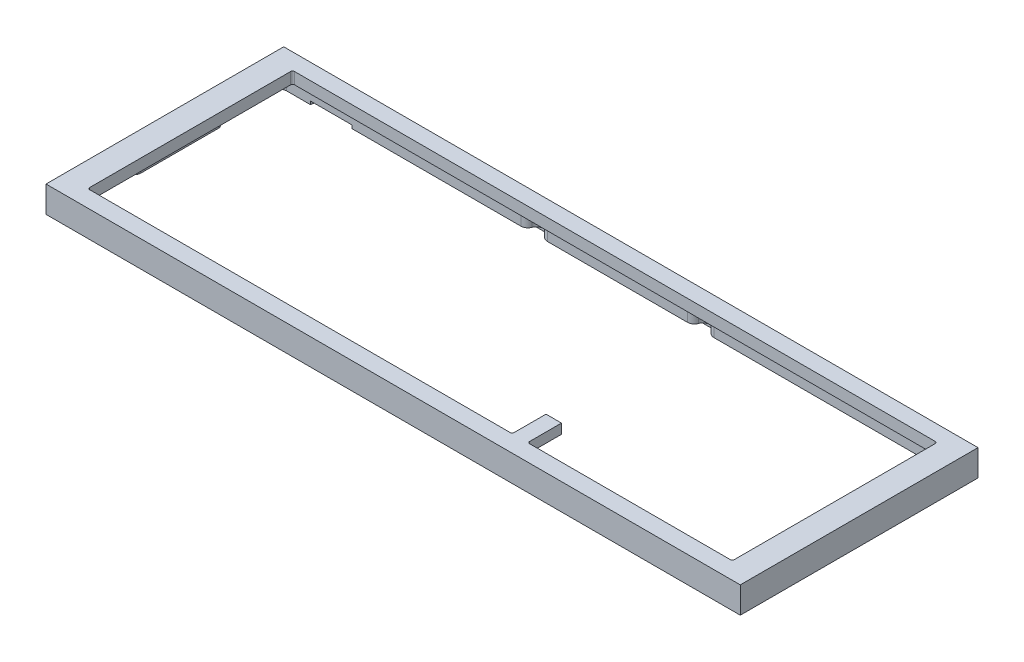
SolidWorks part; units mm, degrees
material "6061 Alloy"
ref_plane "Front Plane" through (0, 0, 0) normal (0, 0, 1) x (1, 0, 0)
ref_plane "Top Plane" through (0, 0, 0) normal (0, 1, 0) x (1, 0, 0)
ref_plane "Right Plane" through (0, 0, 0) normal (1, 0, 0) x (0, 0, -1)
sketch "Sketch1" plane through (0, 0, 0) normal (0, 1, 0) x (1, 0, 0)
  line L1 (0, 0) -> (390.8, 0)
  line L2 (0, 0) -> (0, -133.8)
  line L3 (0, -133.8) -> (390.8, -133.8)
  line L4 (390.8, 0) -> (390.8, -133.8)
  dimension "D1" = 390.8
  dimension "D2" = 133.8
extrude "Boss-Extrude1" add sketch "Sketch1" along normal blind 13.1
sketch "Sketch2" plane through (0, 13.1, 0) normal (0, 1, 0) x (1, 0, 0)
  line L0 (390.8, 0) -> (0, 0) construction
  line L1 (14, -9) -> (376.8, -9)
  line L2 (14, -9) -> (14, -124.3)
  line L3 (14, -124.3) -> (376.8, -124.3)
  line L4 (376.8, -9) -> (376.8, -124.3)
  line L5 (0, -133.8) -> (390.8, -133.8) construction
  line L6 (0, 0) -> (0, -133.8) construction
  line L7 (390.8, -133.8) -> (390.8, 0) construction
  line L8 (390.8, -133.8) -> (390.8, 0) construction
  line L9 (261.6, -124.3) -> (252.9, -124.3)
  line L10 (261.6, -124.3) -> (261.6, -105.25)
  line L11 (261.6, -105.25) -> (252.9, -105.25)
  line L12 (252.9, -124.3) -> (252.9, -105.25)
  line L13 (0, -133.8) -> (390.8, -133.8) construction
  dimension "D1" = 9
  dimension "D2" = 9.5
  dimension "D3" = 14
  dimension "D4" = 14
  dimension "D5" = 129.2
  dimension "D6" = 137.9
  dimension "D7" = 28.55
extrude "Cut-Extrude1" cut sketch "Sketch2" against normal through all contours L3 L12 L11 L10 L4 L1 L2 region at (195.154, 13.1, 66.4586)
sketch "Sketch3" plane through (0, 0, 0) normal (0, -1, 0) x (1, 0, 0)
  line L0 (390.8, 0) -> (0, 0) construction
  line L1 (385.5, 2.6) -> (5.3, 2.6)
  line L2 (385.5, 2.6) -> (385.5, 131.2)
  line L3 (385.5, 131.2) -> (5.3, 131.2)
  line L4 (5.3, 2.6) -> (5.3, 131.2)
  line L5 (390.8, 133.8) -> (390.8, 0) construction
  point P4 (195.4, 2.6)
  point P7 (195.4, 0)
  point P8 (385.5, 66.9)
  point P11 (390.8, 66.9)
  dimension "D1" = 380.2
  dimension "D2" = 128.6
extrude "Cut-Extrude2" cut sketch "Sketch3" against normal blind 6.6 contours L2 L1 L4 L3
sketch "Sketch5" plane through (0, 6.6, 0) normal (0, -1, 0) x (1, 0, 0)
  line L0 (290, 128.2) -> (285, 128.2)
  line L1 (290, 128.2) -> (290, 131.2)
  line L2 (290, 131.2) -> (285, 131.2)
  line L3 (285, 128.2) -> (285, 131.2)
  line L4 (105, 128.2) -> (100, 128.2)
  line L5 (105, 128.2) -> (105, 131.2)
  line L6 (105, 131.2) -> (100, 131.2)
  line L7 (100, 128.2) -> (100, 131.2)
  line L8 (8.3, 45) -> (8.3, 88.8)
  line L9 (382.5, 45) -> (382.5, 88.8)
  line L10 (0, 133.8) -> (390.8, 133.8) construction
  line L11 (5.3, 2.6) -> (5.3, 131.2) construction
  line L12 (390.8, 0) -> (0, 0) construction
  line L13 (385.5, 2.6) -> (385.5, 131.2) construction
  line L15 (385.5, 131.2) -> (5.3, 131.2) construction
  line L16 (385.5, 131.2) -> (5.3, 131.2) construction
  line L17 (385.5, 2.6) -> (5.3, 2.6) construction
  line L18 (5.3, 2.6) -> (5.3, 131.2) construction
  circle A0 centre (102.5, 128.2) radius 2.5
  circle A1 centre (287.5, 128.2) radius 2.5
  circle A2 centre (102.5, 2.6) radius 2.5
  circle A3 centre (195.4, 2.6) radius 2.5
  circle A4 centre (287.5, 2.6) radius 2.5
  circle A5 centre (385.5, 45) radius 3
  circle A6 centre (385.5, 88.8) radius 3
  circle A7 centre (5.3, 45) radius 3
  circle A8 centre (5.3, 88.8) radius 3
  line M9 (5.3, 131.2) -> (5.3, 2.6)
  line M10 (5.3, 2.6) -> (385.5, 2.6)
  line M11 (385.5, 2.6) -> (385.5, 131.2)
  dimension "D1" = 5
  dimension "D5" = 6
  dimension "D2" = 185
  dimension "D3" = 92.9
  dimension "D4" = 185
  dimension "D6" = 45
  dimension "D7" = 97.2
  dimension "D8" = 3
  dimension "D9" = 97.2
  dimension "D10" = 45
  dimension "D11" = 45
extrude "Boss-Extrude2" add sketch "Sketch5" along normal up to surface (6.6 mm away) contours A6 L9 A5 M11 | A5 M11 | A6 M11 | A4 M10 | A3 M10 | A2 M10 | A7 M9 | A8 A7 L8 M9 | A8 M9 | A0 | L7 L6 L5 L4 | L3 L2 L1 L0 | A1 region at (6.8273, 6.6, 66.9) region at (6.5732, 6.6, 45) region at (384.2268, 6.6, 45) region at (287.5, 6.6, 3.661) region at (195.4, 6.6, 3.661) region at (102.5, 6.6, 3.661) region at (6.5732, 6.6, 88.8) region at (383.9727, 6.6, 66.9) region at (384.2268, 6.6, 88.8) up to face at (195.4, 0, 66.9)
sketch "Sketch6" plane through (0, 6.6, 0) normal (0, -1, 0) x (-1, 0, 0)
  line L0 (-195.4, 0) -> (-195.4, -133.8) construction
  line L1 (-390.8, 0) -> (0, 0) construction
  line L2 (0, -133.8) -> (-390.8, -133.8) construction
  line L3 (-390.8, -66.9) -> (0, -66.9) construction
  line L4 (-390.8, -133.8) -> (-390.8, 0) construction
  line L5 (0, 0) -> (0, -133.8) construction
  line L6 (-285, -2.6) -> (-197.9, -2.6) construction
  line L7 (-385.5, -2.6) -> (-385.5, -42) construction
  line L8 (-385.5, -2.6) -> (-385.5, -42) construction
  point P12 (-382.9, -22.7)
  point P13 (-382.9, -111)
  point P14 (-324.8, -129)
  point P15 (-192.2, -129)
  point P16 (-148.6, -5.4)
  point P18 (-64.4, -129)
  point P19 (-7.9, -111)
  point P20 (-7.9, -22.7)
  point P22 (-242.3, -5.4)
  dimension "D1" = 22.8
  dimension "D2" = 22.7
  dimension "D3" = 7.9
  dimension "D4" = 66
  dimension "D5" = 4.8
  dimension "D6" = 198.6
  dimension "D7" = 326.4
  dimension "D8" = 2.8
  dimension "D9" = 143.2
  dimension "D10" = 236.9
sketch "Sketch7" plane through (0, 0, 0) normal (0, -1, 0) x (1, 0, 0)
  arc A0 (382.5, 45) -> (385.5, 42) centre (385.5, 45) ccw construction
  arc A1 (385.5, 91.8) -> (382.5, 88.8) centre (385.5, 88.8) ccw construction
  arc A2 (290, 2.6) -> (285, 2.6) centre (287.5, 2.6) ccw construction
  arc A3 (197.9, 2.6) -> (192.9, 2.6) centre (195.4, 2.6) ccw construction
  arc A4 (105, 2.6) -> (100, 2.6) centre (102.5, 2.6) ccw construction
  arc A5 (5.3, 42) -> (8.3, 45) centre (5.3, 45) ccw construction
  arc A6 (8.3, 88.8) -> (5.3, 91.8) centre (5.3, 88.8) ccw construction
  arc A7 (100, 128.2) -> (105, 128.2) centre (102.5, 128.2) ccw construction
  arc A8 (285, 128.2) -> (290, 128.2) centre (287.5, 128.2) ccw construction
  point P0 (385.5, 45)
  point P1 (385.5, 88.8)
  point P2 (287.5, 128.2)
  point P3 (102.5, 128.2)
  point P4 (5.3, 88.8)
  point P5 (5.3, 45)
  point P6 (102.5, 2.6)
  point P7 (195.4, 2.6)
  point P8 (287.5, 2.6)
sketch "Sketch8" plane through (0, 6.6, 0) normal (0, -1, 0) x (1, 0, 0)
  line L1 (261.6, 105.25) -> (252.9, 105.25)
  line L2 (261.6, 105.25) -> (261.6, 124.3)
  line L3 (261.6, 124.3) -> (252.9, 124.3)
  line L4 (252.9, 105.25) -> (252.9, 124.3)
extrude "Cut-Extrude3" cut sketch "Sketch8" against normal blind 1
hole_wizard "M2x0.4 Tapped Hole2" positions "3DSketch3" profile "Sketch11" tap size "M2x0.4" standard "ANSI Metric"
sketch3d "3DSketch3"
  point P0 (382.9, 6.6, 22.7)
  point P3 (382.9, 6.6, 111)
  point P6 (324.8, 6.6, 129)
  point P9 (192.2, 6.6, 129)
  point P12 (64.4, 6.6, 129)
  point P15 (7.9, 6.6, 22.7)
  point P18 (7.9, 6.6, 111)
  point P22 (242.3, 6.6, 5.4)
  point P25 (148.6, 6.6, 5.4)
sketch "Sketch11" plane through (382.9, 6.6, 22.7) normal (1, 0, 0) x (0, 0, -1)
  line L0 (0, 0) -> (0, 4.4807)
  line L1 (0, 4.4807) -> (0.8, 4)
  line L2 (0.8, 4) -> (0.8, 0)
  line L5 (0.8, 0) -> (0, 0)
  line L10 (0, 4.4807) -> (-0.8, 4) construction
  line L11 (0, -6.35) -> (0, 107.95) construction
  dimension "Tap Drill Dia." = 1.6
  dimension "Tap Drill Depth" = 4
  dimension "Drill Angle" = 118
cosmetic thread "Hole Thread10" parameters "D1"=4, "D2"=2
cosmetic thread "Hole Thread11" parameters "D1"=4, "D2"=2
cosmetic thread "Hole Thread12" parameters "D1"=4, "D2"=2
cosmetic thread "Hole Thread13" parameters "D1"=4, "D2"=2
cosmetic thread "Hole Thread14" parameters "D1"=4, "D2"=2
cosmetic thread "Hole Thread15" parameters "D1"=4, "D2"=2
cosmetic thread "Hole Thread16" parameters "D1"=4, "D2"=2
cosmetic thread "Hole Thread17" parameters "D1"=4, "D2"=2
cosmetic thread "Hole Thread18" parameters "D1"=4, "D2"=2
fillet "Fillet1" radius 4 12 edges at (385.5, 3.3, 42) (385.5, 3.3, 2.6) (5.3, 3.3, 2.6) (5.3, 3.3, 42) (5.3, 3.3, 91.8) (5.3, 3.3, 131.2) (100, 3.3, 131.2) (105, 3.3, 131.2) (290, 3.3, 131.2) (285, 3.3, 131.2) (385.5, 3.3, 131.2) (385.5, 3.3, 91.8)
fillet "Fillet2" radius 1.1 12 edges at (376.8, 9.85, 9) (376.8, 9.85, 124.3) (14, 9.85, 124.3) (14, 9.85, 9) (105, 3.3, 2.6) (100, 3.3, 2.6) (197.9, 3.3, 2.6) (192.9, 3.3, 2.6) (285, 3.3, 2.6) (290, 3.3, 2.6) (261.6, 10.35, 124.3) (252.9, 10.35, 124.3)
sketch "Sketch14" plane through (0, 0, 0) normal (0, -1, 0) x (1, 0, 0)
  line L0 (390.8, 0) -> (0, 0) construction
  line L1 (388.8, 0) -> (2, 0)
  line L2 (388.8, 0) -> (388.8, 131.8)
  line L3 (388.8, 131.8) -> (2, 131.8)
  line L4 (2, 0) -> (2, 131.8)
  line L5 (0, 0) -> (0, 133.8) construction
  line L6 (390.8, 133.8) -> (390.8, 0) construction
  line L7 (0, 133.8) -> (390.8, 133.8) construction
  line L9 (390.8, 0) -> (0, 0)
  line L10 (390.8, 0) -> (390.8, 133.8)
  line L11 (390.8, 133.8) -> (0, 133.8)
  line L12 (0, 0) -> (0, 133.8)
  line L13 (390.8, 0) -> (0, 0)
  line L14 (390.8, 0) -> (390.8, 2)
  line L15 (390.8, 2) -> (0, 2)
  line L16 (0, 0) -> (0, 2)
  line M21 (0, 0) -> (390.8, 0)
  line M22 (390.8, 0) -> (390.8, 133.8)
  line M25 (0, 0) -> (390.8, 0)
  dimension "D1" = 2
  dimension "D2" = 2
  dimension "D3" = 2
  dimension "D4" = 2
extrude "Boss-Extrude3" add sketch "Sketch14" along normal blind 1.7 contours L12 L9 L4 L3 L2 L10 L11 | L2 L15 L4 M25 M21 | L15 L2 M22 M21 | L4 L15 L12 M25 region at (195.4, 0, 1) region at (389.8, 0, 1) region at (1, 0, 1) region at (389.2124, 0, 66.9)
sketch "Sketch16" plane through (0, 6.6, 0) normal (0, -1, 0) x (1, 0, 0)
  line L0 (5.3, 6.6) -> (5.3, 39.2554) construction
  line L1 (385.5, 2.6) -> (5.3, 2.6)
  line L2 (385.5, 2.6) -> (385.5, 7.6)
  line L3 (385.5, 7.6) -> (5.3, 7.6)
  line L4 (5.3, 2.6) -> (5.3, 7.6)
  line L5 (385.5, 6.6) -> (385.5, 39.2554) construction
  line L6 (381.5, 2.6) -> (290.9278, 2.6) construction
  line L7 (246.3, 6.4) -> (246.3, 7.6)
  line L8 (238.3, 6.4) -> (238.3, 7.6)
  line L9 (152.6, 6.4) -> (152.6, 7.6)
  line L10 (144.6, 6.4) -> (144.6, 7.6)
  circle A0 centre (242.3, 6.4) radius 4
  circle A1 centre (148.6, 6.4) radius 4
  point P24 (242.3, 5.4)
  point P26 (148.6, 5.4)
  dimension "D2" = 8
  dimension "D1" = 5
  dimension "D3" = 1.2
  dimension "D4" = 1.2
extrude "Boss-Extrude4" add sketch "Sketch16" along normal up to surface (6.6 mm away) contours A0 L1 L2 L3 L7 | A1 L1 A0 L8 L3 L9 | A1 L10 L3 L4 L1 region at (315.6181, 6.6, 5.0935) region at (195.45, 6.6, 5.079) region at (75.2319, 6.6, 5.0935) up to face at (195.4, 0, 66.9)
sketch "Sketch17" plane through (0, 6.6, 0) normal (0, -1, 0) x (1, 0, 0)
  circle A0 centre (148.6, 6.4) radius 4
  circle A1 centre (242.3, 6.4) radius 4
  arc A2 (149.849, 2.6) -> (152.6, 6.4) centre (148.6, 6.4) ccw construction
  dimension "D1" = 8
  dimension "D2" = 1
extrude "Cut-Extrude5" cut sketch "Sketch17" along normal up to surface (6.6 mm away) up to face at (195.3316, 0, 64.1007)
sketch "Sketch18" plane through (0, 0, 0) normal (0, 0, -1) x (-1, 0, 0)
  line L0 (0, -1.7) -> (-390.8, -1.7) construction
  line L1 (-40.3, -1.7) -> (-28.3, -1.7)
  line L2 (-40.3, -1.7) -> (-40.3, 1.8)
  line L3 (-40.3, 1.8) -> (-28.3, 1.8)
  line L4 (-28.3, -1.7) -> (-28.3, 1.8)
  line L5 (0, 13.1) -> (0, -1.7) construction
  point P6 (-34.3, 1.8)
  dimension "D1" = 12
  dimension "D2" = 3.5
  dimension "D3" = 34.3
extrude "Cut-Extrude6" cut sketch "Sketch18" against normal blind 10
fillet "Fillet4" radius 4 4 edges at (144.6, 3.3, 7.6) (152.6, 3.3, 7.6) (238.3, 3.3, 7.6) (246.3, 3.3, 7.6)
hole_wizard "M2x0.4 Tapped Hole3" positions "3DSketch2" profile "Sketch10" tap size "M2x0.4" standard "ANSI Metric"
sketch3d "3DSketch2"
  line L0 (390.8, -1.7, 0) -> (390.8, -1.7, 133.8) construction
  line L1 (0, -1.7, 133.8) -> (0, -1.7, 0) construction
  line L7 (388.8, 0, 2) -> (40.3, 0, 2) construction
  point P0 (385.5, 0, 45)
  point P3 (385.5, 0, 88.8)
  point P6 (287.5, 0, 128.2)
  point P9 (102.5, 0, 128.2)
  point P12 (5.3, 0, 88.8)
  point P15 (5.3, 0, 45)
  point P30 (312.8185, 0, 4.3)
  point P32 (195.4074, 0, 4.3)
  point P34 (77.9815, 0, 4.3)
  dimension "D1" = 78
  dimension "D2" = 78
  dimension "D3" = 195.4
  dimension "D4" = 2.3
sketch "Sketch10" plane through (385.5, 0, 45) normal (1, 0, 0) x (0, 0, -1)
  line L0 (0, 0) -> (0, 4.4807)
  line L1 (0, 4.4807) -> (0.8, 4)
  line L2 (0.8, 4) -> (0.8, 0)
  line L5 (0.8, 0) -> (0, 0)
  line L10 (0, 4.4807) -> (-0.8, 4) construction
  line L11 (0, -6.35) -> (0, 107.95) construction
  dimension "Tap Drill Dia." = 1.6
  dimension "Tap Drill Depth" = 4
  dimension "Drill Angle" = 118
cosmetic thread "Hole Thread4" parameters "D1"=4, "D2"=2
cosmetic thread "Hole Thread5" parameters "D1"=4, "D2"=2
cosmetic thread "Hole Thread6" parameters "D1"=4, "D2"=2
cosmetic thread "Hole Thread7" parameters "D1"=4, "D2"=2
cosmetic thread "Hole Thread8" parameters "D1"=4, "D2"=2
cosmetic thread "Hole Thread9" parameters "D1"=4, "D2"=2
cosmetic thread "Hole Thread19" parameters "D1"=4, "D2"=2
cosmetic thread "Hole Thread20" parameters "D1"=4, "D2"=2
cosmetic thread "Hole Thread21" parameters "D1"=4, "D2"=2
fillet "Fillet5" radius 4 6 edges at (5.3, 3.3, 7.6) (385.5, 3.3, 7.6) (388.8, -0.85, 2) (388.8, -0.85, 131.8) (2, -0.85, 131.8) (2, -0.85, 2)
sketch "Sketch20" plane through (0, 0, 0) normal (0, -1, 0) x (1, 0, 0)
  line L2 (40.3, 2) -> (40.3, 7.6)
  line L3 (40.3, 7.6) -> (45.9, 7.6)
  line L4 (28.3, 2) -> (28.3, 7.6)
  line L5 (28.3, 7.6) -> (22.7, 7.6)
  line L6 (384.8, 2) -> (40.3, 2) construction
  circle A0 centre (40.3, 7.6) radius 5.6
  circle A1 centre (28.3, 7.6) radius 5.6
extrude "Cut-Extrude7" cut sketch "Sketch20" against normal up to surface (1.8 mm away) contours L2 A0 L3 | L5 A1 L4 region at (42.6767, 0, 5.2233) region at (25.9233, 0, 5.2233) up to face at (34.3, 1.8, 3.8)
